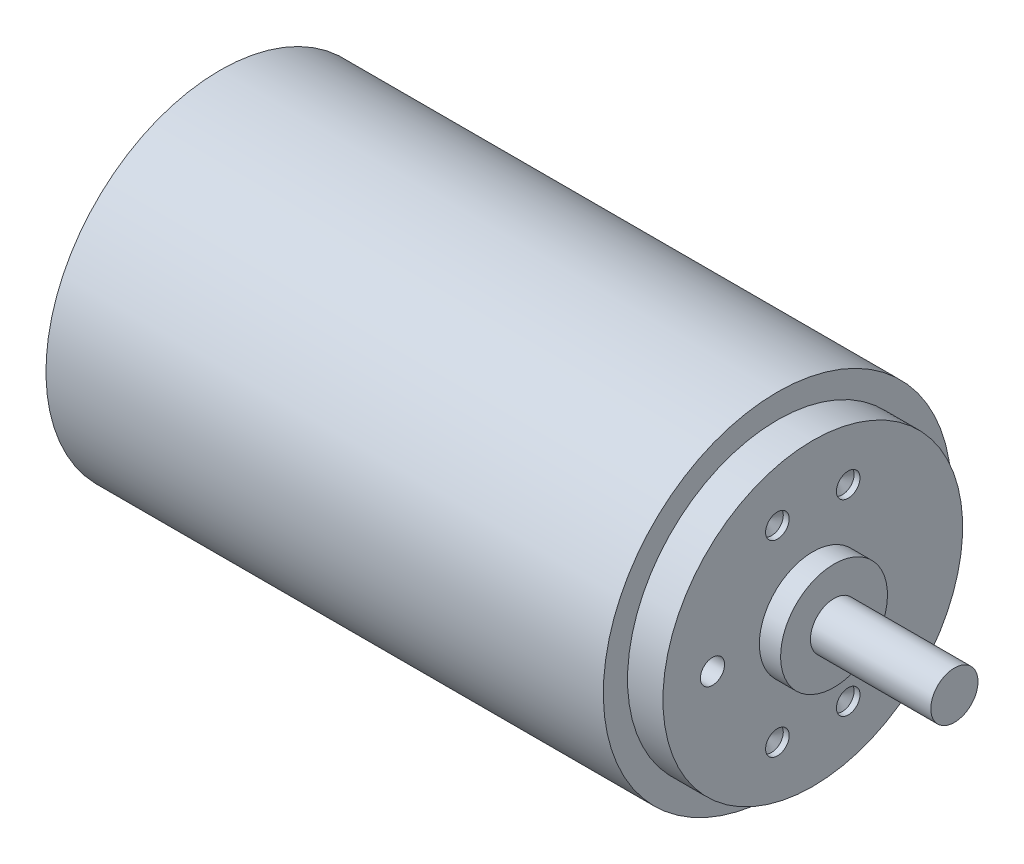
SolidWorks part; units mm, degrees
ref_plane "Ebene vorne" through (0, 0, 0) normal (0, 0, 1) x (1, 0, 0)
ref_plane "Ebene oben" through (0, 0, 0) normal (0, 1, 0) x (1, 0, 0)
ref_plane "Ebene rechts" through (0, 0, 0) normal (1, 0, 0) x (0, 0, -1)
sketch "Skizze1" plane through (0, 0, 0) normal (0, 0, 1) x (1, 0, 0)
  line L6 (-21.6511, 29.5) -> (72.8088, 29.5)
  line L7 (72.8088, 29.5) -> (72.8088, 25.3976)
  line L8 (72.8088, 25.3976) -> (78.8088, 25.3976)
  line L9 (78.8088, 25.3976) -> (78.8088, 9.0539)
  line L10 (87.8808, 4) -> (102.8088, 4)
  line L11 (102.8088, 4) -> (102.8088, 0)
  line L12 (102.8088, 0) -> (0, 0)
  line L13 (0, 0) -> (-39.1912, 0)
  line L14 (-21.6511, 29.5) -> (-21.6511, 22.9497)
  line L15 (-24.1912, 22.9497) -> (-21.6511, 22.9497)
  line L16 (-24.1912, 22.9497) -> (-24.1912, 5.6934)
  line L17 (-24.1912, 5.6934) -> (-30.1912, 4)
  line L18 (-30.1912, 4) -> (-39.1912, 4)
  line L19 (-39.1912, 4) -> (-39.1912, 0)
  line L20 (78.8088, 9.0539) -> (82.4088, 9.0539)
  line L21 (82.4088, 9.0539) -> (82.4088, 4)
  line L22 (82.4088, 4) -> (87.8808, 4)
  point P1 (-24.9433, 21.9015)
  point P2 (-40.095, 0)
  dimension "D1" = 103
  dimension "D2" = 142
  dimension "D3" = 4
  dimension "D4" = 6
  dimension "D5" = 3.6
  dimension "D6" = 20.4
  dimension "D7" = 29.5
  dimension "D8" = 4
  dimension "D9" = 15
revolve "Rotation1" add sketch "Skizze1" angle 360 about L13
hole_wizard "Ø4.0 (4) Durchmesser Bohrung1" positions "Skizze4" profile "Skizze3" hole size "Ø4.0" standard "ISO"
sketch "Skizze4" plane through (78.8088, 0, 0) normal (1, 0, 0) x (0, 0, -1)
  line L0 (0, 0) -> (0, 39.7142) construction
  line L1 (0, 39.7142) -> (0, 0) construction
  line L2 (0, 0) -> (0, -47.571) construction
  circle A0 centre (0, 0) radius 17 construction
  point P0 (-6, 15.906)
  point P2 (6, 15.906)
  point P6 (-6, -15.906)
  point P8 (6, -15.906)
  dimension "D1" = 34
  dimension "D2" = 6
  dimension "D3" = 6
  dimension "D4" = 6
  dimension "D5" = 6
sketch "Skizze3" plane through (78.8088, 15.906, 6) normal (0, 1, 0) x (0, 0, -1)
  line L0 (0, 0) -> (0, 2.2017)
  line L1 (0, 2.2017) -> (2, 1)
  line L2 (2, 1) -> (2, 0)
  line L5 (2, 0) -> (0, 0)
  line L10 (0, 2.2017) -> (-2, 1) construction
  line L11 (0, -6.35) -> (0, 107.95) construction
  dimension "Bohrerdurchmesser" = 4
  dimension "Bohrungstiefe" = 1
  dimension "Spitzenwinkel" = 118
hole_wizard "Ø4.1 (4.1) Durchmesser Bohrung1" positions "Skizze5" profile "Skizze6" hole size "Ø4.1" standard "ISO"
sketch "Skizze5" plane through (78.8088, 0, 0) normal (1, 0, 0) x (0, 0, -1)
  point P0 (-17, 0)
  dimension "D1" = 17
sketch "Skizze6" plane through (78.8088, 0, 17) normal (0, 1, 0) x (0, 0, -1)
  line L0 (0, 0) -> (0, 12.7318)
  line L1 (0, 12.7318) -> (2.05, 11.5)
  line L2 (2.05, 11.5) -> (2.05, 0)
  line L5 (2.05, 0) -> (0, 0)
  line L10 (0, 12.7318) -> (-2.05, 11.5) construction
  line L11 (0, -6.35) -> (0, 107.95) construction
  dimension "Bohrerdurchmesser" = 4.1
  dimension "Bohrungstiefe" = 11.5
  dimension "Spitzenwinkel" = 118
